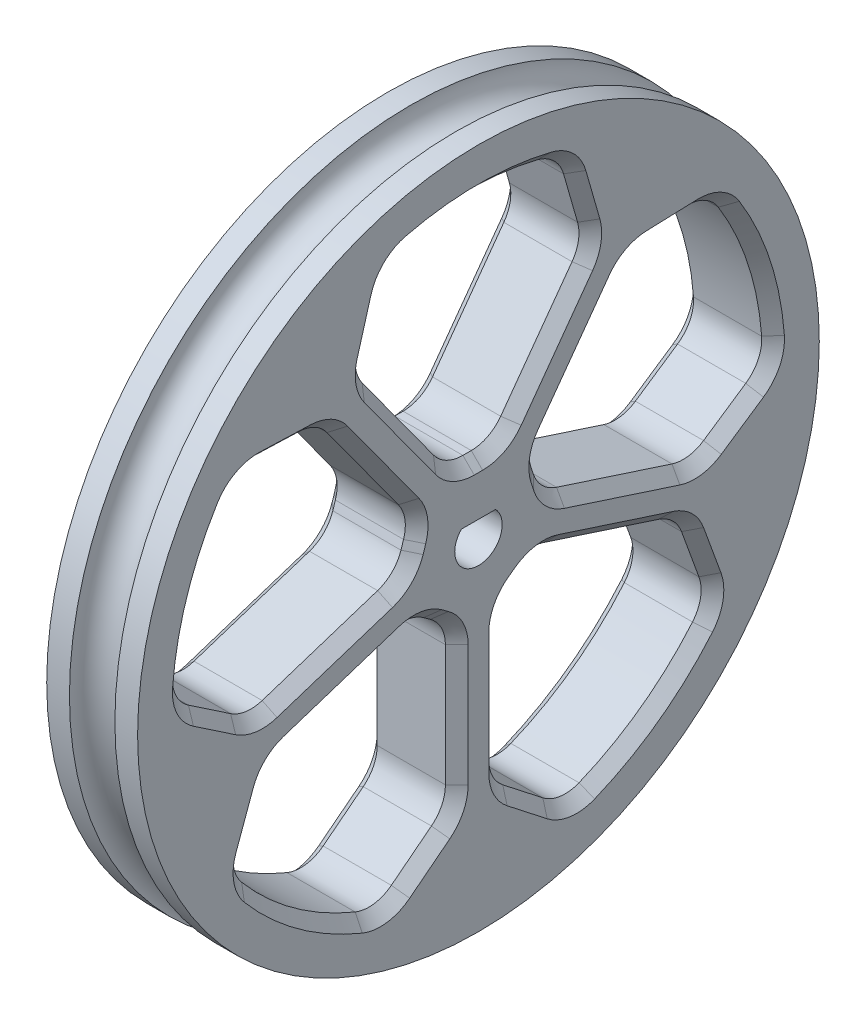
SolidWorks part; units mm, degrees
ref_plane "Front Plane" through (0, 0, 0) normal (0, 0, 1) x (1, 0, 0)
ref_plane "Top Plane" through (0, 0, 0) normal (0, 1, 0) x (1, 0, 0)
ref_plane "Right Plane" through (0, 0, 0) normal (1, 0, 0) x (0, 0, -1)
sketch "Sketch1" plane through (0, 0, 0) normal (0, 0, 1) x (1, 0, 0)
  line L0 (-3.175, 23.8125) -> (-1.5875, 23.8125)
  line L1 (-1.5875, 23.8125) -> (-1.5875, 22.225) construction
  line L2 (-3.175, 23.8125) -> (-3.175, 0)
  line L3 (-3.175, 0) -> (3.175, 0)
  line L4 (3.175, 23.8125) -> (3.175, 0)
  line L5 (-1.5875, 22.225) -> (1.5875, 22.225) construction
  line L6 (1.5875, 22.225) -> (1.5875, 23.8125) construction
  line L7 (1.5875, 23.8125) -> (3.175, 23.8125)
  arc A0 (-1.5875, 23.8125) -> (1.5875, 23.8125) centre (0, 23.8125) ccw
  dimension "D1" = 3.175
  dimension "D2" = 6.35
  dimension "D3" = 22.225
  dimension "D4" = 23.8125
revolve "Revolve1" add sketch "Sketch1" angle 360 about L3
sketch "Sketch3" plane through (0, 0, 0) normal (1, 0, 0) x (0, 0, -1)
  line L0 (0, 20.6375) -> (0, 0) construction
  line L1 (6.35, 19.6363) -> (8.0603, 13.6716)
  line L2 (8.0603, 13.6716) -> (1.5875, 4.7625)
  line L3 (1.1979, 1.1437) -> (-1.1979, 1.1437)
  line L4 (1.5875, 4.7625) -> (-1.5875, 4.7625)
  line L5 (-1.5875, 4.7625) -> (-8.0603, 13.6716)
  line L6 (-8.0603, 13.6716) -> (-6.35, 19.6363)
  line L7 (0, 0) -> (12.1304, 16.6961) construction
  line L8 (0, 0) -> (-12.1304, 16.6961) construction
  circle A0 centre (0, 0) radius 20.6375 construction
  arc A1 (-1.1979, 1.1437) -> (1.1979, 1.1437) centre (0, 0) ccw
  arc A2 (6.35, 19.6363) -> (-6.35, 19.6363) centre (0, 0) ccw
  point P14 (0, 4.7625)
  point P42 (0, 0)
  dimension "D1" = 1.6563
  dimension "D3" = 2.8
  dimension "D4" = 72
  dimension "D5" = 3.175
  dimension "D6" = 16
  dimension "D7" = 4.7625
  dimension "D8" = 12.7
extrude "Cut-Extrude1" cut sketch "Sketch3" along normal up to surface and the other way up to surface contours L1 A2 L6 L5 L4 L2 region at (0, 13.6892, 0) up to face at (3.175, 0, 23.8125) other way up to face at (-3.175, 0, 23.8125)
extrude "Cut-Extrude2" cut sketch "Sketch3<3>" along normal up to surface and the other way up to surface contours A1 L3 up to face at (3.175, 12.857, 0) other way up to face at (-3.175, 12.857, 0)
sketch "Sketch3<3>" plane through (0, 0, 0) normal (1, 0, 0) x (0, 0, -1) same geometry as "Sketch3"
fillet "Fillet1" radius 2.54 6 edges at (0, 19.6363, 6.35) (0, 13.6716, 8.0603) (0, 4.7625, 1.5875) (0, 4.7625, -1.5875) (0, 13.6716, -8.0603) (0, 19.6363, -6.35)
chamfer "Chamfer1" distance 0.7937 angle 45 24 edges at (-3.175, 16.5712, -7.2289) (-3.175, 20.6375, 0) (-3.175, 16.5712, 7.2289) (-3.175, 9.2394, 4.8402) (-3.175, 4.7625, 0) (-3.175, 9.2394, -4.8402) (3.175, 9.2394, -4.8402) (3.175, 4.7625, 0) (3.175, 9.2394, 4.8402) (3.175, 16.5712, 7.2289) (3.175, 20.6375, 0) (3.175, 16.5712, -7.2289) (3.175, 5.0393, 1.4464) (3.175, 13.7213, 7.7787) (3.175, 5.0393, -1.4464) (3.175, 19.4111, 6.0575) (3.175, 13.7213, -7.7787) (3.175, 19.4111, -6.0575) (-3.175, 5.0393, 1.4464) (-3.175, 5.0393, -1.4464) (-3.175, 13.7213, 7.7787) (-3.175, 13.7213, -7.7787) (-3.175, 19.4111, 6.0575) (-3.175, 19.4111, -6.0575)
ref_axis "Axis1" through (-1.5875, 0, 0) along (-1, 0, 0)
pattern_circular "CirPattern3" count 5 every 72 about axis through (-1.5875, 0, 0) along (-1, 0, 0) of "Cut-Extrude1", "Chamfer1", "Fillet1"
equation "\"D1@Sketch3\"=(3.25mm + .0625mm)/2"
